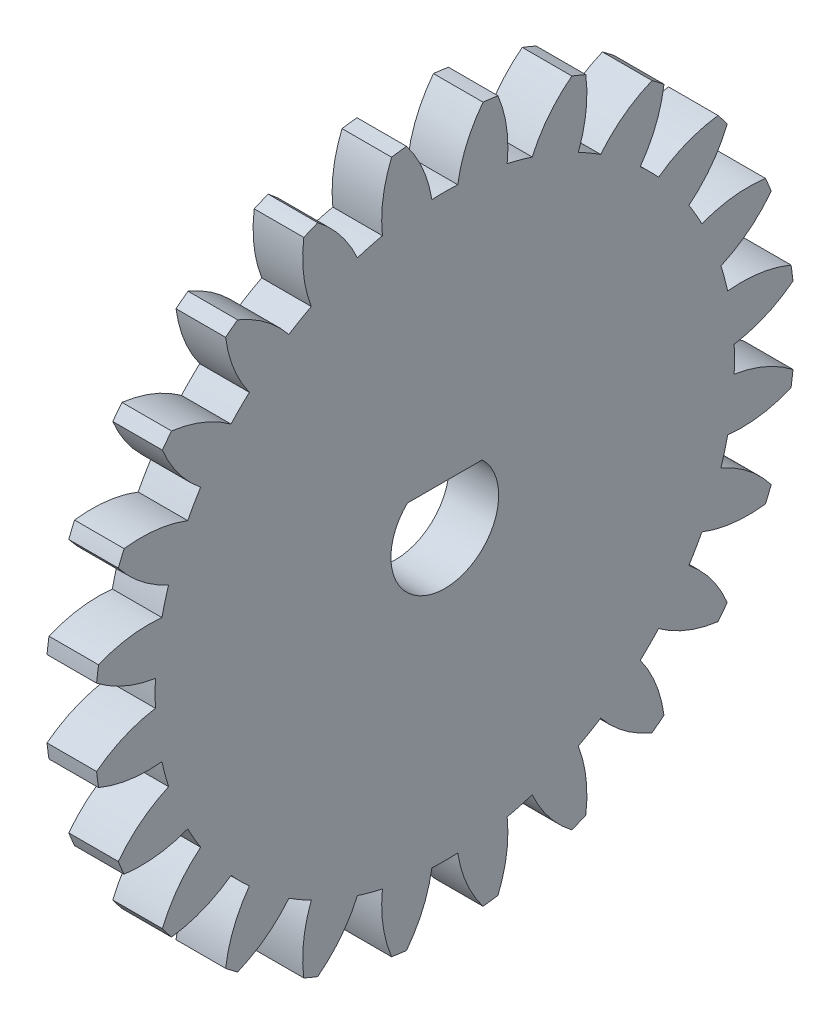
SolidWorks part; units mm, degrees
ref_plane "Plane1" through (0, 0, 0) normal (0, 0, 1) x (1, 0, 0)
ref_plane "Plane2" through (0, 0, 0) normal (0, 1, 0) x (1, 0, 0)
ref_plane "Plane3" through (0, 0, 0) normal (1, 0, 0) x (0, 0, -1)
sketch "HoldingSke" plane through (0, 0, 0) normal (0, 1, 0) x (1, 0, 0)
  line L0 (0, 0) -> (185.6324, -82.6489)
  line L1 (-15, 0) -> (100, 0) construction
  line L2 (0, 0) -> (-2.1039, 2.3779)
  line L3 (0, 0) -> (-11.863, 4.5341)
  line L4 (0, 0) -> (7.8894, 3.5126)
  line L5 (0, 0) -> (-47.5972, -17.7524)
  line L6 (0, 0) -> (-4.8428, -3.2675)
  line L7 (-2.1039, 2.3779) -> (8.8308, 51.9871)
  line L8 (-76.2, 54.61) -> (-61.976, 54.61)
  line L9 (-71.009, 38.7566) -> (-53.1078, 45.2721)
  line L10 (-76.2, 71.12) -> (104.1128, 71.12)
  line L11 (0, 0) -> (-5.842, 0)
  line L12 (-76.2, 101.6) -> (-76.0857, 101.6)
  line L13 (24.9733, 27.94) -> (52.9518, 28.4284)
  line L14 (24.9733, 27.94) -> (24.9746, 27.94)
  line L15 (24.9733, 27.94) -> (100.4006, 29.5858)
  circle A0 centre (0, 0) radius 6.35
  circle A1 centre (0, 0) radius 34.13
  circle A2 centre (0, 0) radius 38.1
  circle A3 centre (0, 0) radius 6.35
  dimension "Num_teeth" = 24
  dimension "H" = 19.05
  dimension "Pitch_radius" = 180.3128
  dimension "Width" = 5.842
  dimension "Thickness" = 5.842
sketch "BasProSke" plane through (0, 0, 0) normal (0, 1, 0) x (1, 0, 0)
  line L0 (-10, 0) -> (60, 0) construction
  line L1 (0, 0) -> (0, 41.275)
  line L2 (0, 0) -> (5.842, 0)
  line L3 (5.842, 0) -> (5.842, 41.275)
  line L4 (5.842, 41.275) -> (0, 41.275)
  dimension "Thickness" = 5.842
  dimension "Diameter" = 82.55
revolve "Base-Revolve" add sketch "BasProSke" angle 360 about L0
sketch "TooCutSke" plane through (0, 0, 0) normal (1, 0, 0) x (0, 0, -1)
  line L1 (0, 0) -> (0, 107) construction
  line L2 (0, 0) -> (-2.6918, 38.0048) construction
  line L3 (0, 0) -> (-9.9281, 75.4113) construction
  line L4 (-2.6918, 38.0048) -> (-4.964, 37.7056) construction
  arc A0 (1.5253, 34.0959) -> (-1.5253, 34.0959) centre (0, 0) ccw
  arc A1 (4.5232, 41.052) -> (-4.5232, 41.052) centre (0, 0) ccw
  circle A2 centre (0, 0) radius 38.1 construction
  circle A3 centre (0, 0) radius 35.8023 construction
  arc A4 (-1.5253, 34.0959) -> (-4.5232, 41.052) centre (-16.5807, 31.7314) ccw
  arc A5 (4.5232, 41.052) -> (1.5253, 34.0959) centre (16.5807, 31.7314) ccw
extrude "ToothCut" cut sketch "TooCutSke" along normal through all
fillet "Breaks" [suppressed] radius 0.0635 tangent propagation no
fillet "RootFillets" [suppressed] radius 0.795
pattern_circular "TeethCuts" count 24 every 15 about axis through (-10, 0, 0) along (1, 0, 0) of "ToothCut", "RootFillets", "Breaks"
sketch "HubNeaOneSke" plane through (0, 0, 0) normal (-1, 0, 0) x (0, 0, 1)
  circle A0 centre (0, 0) radius 34.13
  dimension "Diameter" = 68.26
extrude "HubNearOne" [suppressed] add sketch "HubNeaOneSke" along normal blind 44.9581
sketch "HubNeaBotSke" plane through (0, 0, 0) normal (-1, 0, 0) x (0, 0, 1)
  circle A0 centre (0, 0) radius 34.13
  dimension "Diameter" = 68.26
extrude "HubNearBoth" [suppressed] add sketch "HubNeaBotSke" along normal blind 22.479
ref_plane "FarPln" through (5.842, 0, 0) normal (1, 0, 0) x (0, 0, -1)
sketch "HubFarSke" plane through (5.842, 0, 0) normal (1, 0, 0) x (0, 0, -1)
  circle A0 centre (0, 0) radius 34.13
  dimension "Diameter" = 68.26
extrude "HubFar" [suppressed] add sketch "HubFarSke" along normal blind 22.479
sketch "BorSke" plane through (0, 0, 0) normal (1, 0, 0) x (0, 0, -1)
  circle A0 centre (0, 0) radius 6.35
  dimension "Diameter" = 12.7
extrude "Bore" cut sketch "BorSke" along normal mid plane 101.6001
sketch "KeySke" plane through (0, 0, 0) normal (1, 0, 0) x (0, 0, -1)
  line L0 (-1.5875, 0) -> (-1.5875, 7.874)
  line L1 (-1.5875, 7.874) -> (1.5875, 7.874)
  line L2 (1.5875, 7.874) -> (1.5875, 0)
  line L3 (0, 0) -> (0, 34) construction
  line L4 (-1.5875, 0) -> (1.5875, 0)
  dimension "Width" = 3.175
extrude "Keyway" [suppressed] cut sketch "KeySke" along normal mid plane 101.6001
pattern_circular "Keyway2" [suppressed] count 2 every 90 about axis through (-10, 0, 0) along (1, 0, 0) reverse direction yes
sketch "Sketch1" plane through (5.842, 0, 0) normal (1, 0, 0) x (0, 0, -1)
  line L0 (-4.4067, 4.572) -> (4.4067, 4.572)
  arc A0 (4.4067, 4.572) -> (-4.4067, 4.572) centre (0, 0) ccw
  point P5 (0, 4.572)
  point P6 (0, -6.35)
  dimension "D1" = 10.922
extrude "Boss-Extrude1" add sketch "Sketch1" against normal up to surface (5.842 mm away) up to face at (0, 0, -6.35)
equation "' \"Pitch@HoldingSke\" = 4"
equation "' \"Num_teeth@HoldingSke\" = 12"
equation "' \"Ap@HoldingSke\" =  20"
equation "' \"Ap@HoldingSke\" = 20"
equation "' \"Width@HoldingSke\" = 0.5"
equation "' \"Hub_dia@HoldingSke\"= 1"
equation "' \"Hub_dia@HoldingSke\" = 1"
equation "' \"Overall_len@HoldingSke\" = 1.0"
equation "' \"Bore@HoldingSke\" = 0.75"
equation "' \"T_dim@HoldingSke\" = 0.85"
equation "' \"Width@KeySke\" = 0.25"
equation "' \"Show_teeth@HoldingSke\" = 13"
equation "' \"Backlash@HoldingSke\" = 0.009"
equation "' \"Addendum_fac@HoldingSke\" = 1.0"
equation "' \"Dedendum_fac@HoldingSke\" = 1.25"
equation "' \"Dedendum_add@HoldingSke\" = 0.00005"
equation "' \"Clearance_fac@HoldingSke\" = 0.25"
equation "' \"Pitch@HoldingSke\" = 0.5"
equation "' \"Num_teeth@HoldingSke\" = 23"
equation "' \"Show_teeth@HoldingSke\" = 23"
equation "' \"Backlash@HoldingSke\" = 0.0375"
equation "\"Overcut_dia@TooCutSke\" = (\"Num_teeth@HoldingSke\" + 2 * \"Addendum_fac@HoldingSke\") / \"Pitch@HoldingSke\" + 0.002"
equation "\"Pitch_dia@TooCutSke\" = \"Num_teeth@HoldingSke\" / \"Pitch@HoldingSke\""
equation "\"Base_dia@TooCutSke\" = \"Num_teeth@HoldingSke\" / \"Pitch@HoldingSke\" * cos((\"Ap@HoldingSke\"  * 3.14159265 / 180))"
equation "\"Root_dia@TooCutSke\" = (\"Num_teeth@HoldingSke\" + 2) / \"Pitch@HoldingSke\" - 2 * (\"Addendum_fac@HoldingSke\" + \"Dedendum_fac@HoldingSke\") / \"Pitch@HoldingSke\" - \"Dedendum_add@HoldingSke\" * 2"
equation "\"Half_ang@TooCutSke\" = 180 / \"Num_teeth@HoldingSke\""
equation "\"Half_CT@TooCutSke\" = \"Num_teeth@HoldingSke\" / \"Pitch@HoldingSke\" * sin((3.14159265 / 2 / \"Num_teeth@HoldingSke\")) / 2 - 7 * \"Backlash@HoldingSke\" / 4"
equation "\"Flank_rad@TooCutSke\" = \"Num_teeth@HoldingSke\" / \"Pitch@HoldingSke\" / 5"
equation "\"Radius@RootFillets\" = \"Clearance_fac@HoldingSke\" / \"Pitch@HoldingSke\" + \"Dedendum_add@HoldingSke\""
equation "\"Break_rad@Breaks\" = 0.02 / \"Pitch@HoldingSke\""
equation "\"Thickness@HoldingSke\" = \"Width@HoldingSke\""
equation "\"OAL@HoldingSke\" = \"Thickness@HoldingSke\""
equation "\"MHD@HoldingSke\" = (\"Num_teeth@HoldingSke\" + 2) / \"Pitch@HoldingSke\" - 2 * (\"Addendum_fac@HoldingSke\" + \"Dedendum_fac@HoldingSke\")  / \"Pitch@HoldingSke\" - \"Dedendum_add@HoldingSke\" * 2"
equation "\"MBD@HoldingSke\" = (\"Num_teeth@HoldingSke\" + 2) / \"Pitch@HoldingSke\" - 2 * (\"Addendum_fac@HoldingSke\" + \"Dedendum_fac@HoldingSke\")  / \"Pitch@HoldingSke\" - \"Dedendum_add@HoldingSke\" * 2 - 0.002"
equation "\"MHD@HoldingSke\" = ((sgn( \"MHD@HoldingSke\" - \"Hub_dia@HoldingSke\" )-1)*( \"MHD@HoldingSke\" - \"Hub_dia@HoldingSke\" ))/-2+ \"Hub_dia@HoldingSke\""
equation "\"MBD@HoldingSke\" = ((sgn( \"MBD@HoldingSke\" - \"Bore@HoldingSke\" )-1)*( \"MBD@HoldingSke\" - \"Bore@HoldingSke\" ))/-2+ \"Bore@HoldingSke\""
equation "\"OAL@HoldingSke\" = ((sgn( \"OAL@HoldingSke\" - \"Overall_len@HoldingSke\" )+1)*( \"OAL@HoldingSke\" - \"Overall_len@HoldingSke\" ))/2 + \"Overall_len@HoldingSke\" + 0.000002"
equation "\"Num_teeth@TeethCuts\" = int( \"Show_teeth@HoldingSke\" ) + 1"
equation "\"Num_teeth@TeethCuts\" = ((sgn( \"Num_teeth@TeethCuts\" - \"Num_teeth@HoldingSke\" )-1)*( \"Num_teeth@TeethCuts\" - \"Num_teeth@HoldingSke\" ))/-2+ \"Num_teeth@HoldingSke\""
equation "\"Num_teeth@TeethCuts\" = ((sgn( \"Num_teeth@TeethCuts\" - 2.0)+1)*( \"Num_teeth@TeethCuts\" - 2.0))/2 +2.0"
equation "\"Angle@TeethCuts\" = 360.0 / \"Num_teeth@HoldingSke\""
equation "\"Diameter@BasProSke\" = (\"Num_teeth@HoldingSke\" + 2 * \"Addendum_fac@HoldingSke\") / \"Pitch@HoldingSke\""
equation "\"Thickness@BasProSke\"  = \"Thickness@HoldingSke\""
equation "' \"Fillet_rad@BasProSke\" =  \"Thickness@HoldingSke\" * 0.05"
equation "' \"Fillet_rad@BasProSke\" = \"Thickness@HoldingSke\" * 0.05"
equation "\"MHD@HoldingSke\" = ((sgn( \"MHD@HoldingSke\" - \"Root_dia@TooCutSke\" )-1)*( \"MHD@HoldingSke\" - \"Root_dia@TooCutSke\" ))/-2+ \"Root_dia@TooCutSke\""
equation "\"Diameter@HubNeaOneSke\" = \"MHD@HoldingSke\""
equation "\"Length@HubNearOne\" = \"OAL@HoldingSke\" - \"Thickness@BasProSke\""
equation "\"Diameter@HubNeaBotSke\" = \"MHD@HoldingSke\""
equation "\"Length@HubNearBoth\" = ( \"OAL@HoldingSke\" - \"Thickness@BasProSke\" ) / 2.0"
equation "\"Thickness@FarPln\" = \"Thickness@BasProSke\""
equation "\"Diameter@HubFarSke\" = \"MHD@HoldingSke\""
equation "\"Length@HubFar\" = ( \"OAL@HoldingSke\" - \"Thickness@BasProSke\" ) / 2.0"
equation "\"Diameter@BorSke\" = \"MBD@HoldingSke\""
equation "\"D1@Bore\" = \"OAL@HoldingSke\" * 2.0"
equation "\"D1@Keyway\" = \"OAL@HoldingSke\" * 2.0"
equation "\"Offset@KeySke\" = \"T_dim@HoldingSke\" - \"MBD@HoldingSke\" / 2.0"
